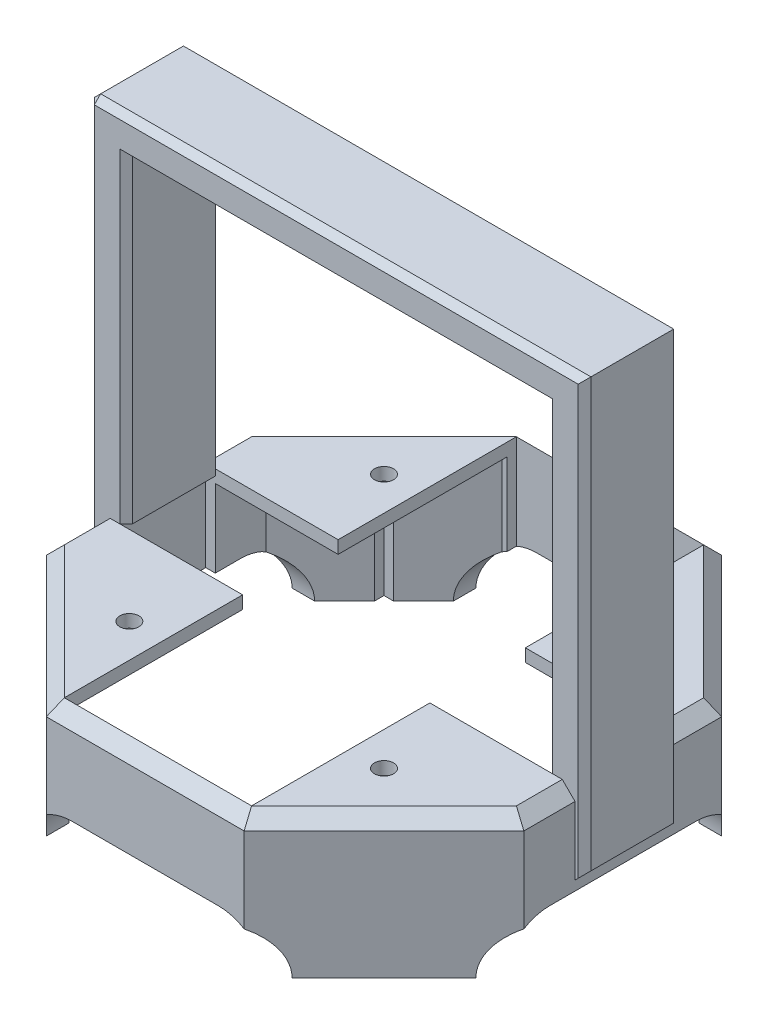
SolidWorks part; units mm, degrees
ref_plane "Front Plane" through (0, 0, 0) normal (0, 0, 1) x (1, 0, 0)
ref_plane "Top Plane" through (0, 0, 0) normal (0, 1, 0) x (1, 0, 0)
ref_plane "Right Plane" through (0, 0, 0) normal (1, 0, 0) x (0, 0, -1)
sketch "Sketch1" plane through (0, 0, 0) normal (0, 1, 0) x (1, 0, 0)
  line L1 (15.533, 37.5) -> (-15.533, 37.5)
  line L2 (-15.533, 37.5) -> (-37.5, 15.533)
  line L3 (-37.5, 15.533) -> (-37.5, -15.533)
  line L4 (-37.5, -15.533) -> (-15.533, -37.5)
  line L5 (-15.533, -37.5) -> (15.533, -37.5)
  line L6 (15.533, -37.5) -> (37.5, -15.533)
  line L7 (37.5, -15.533) -> (37.5, 15.533)
  line L8 (37.5, 15.533) -> (15.533, 37.5)
  circle A0 centre (0, 0) radius 37.5 construction
  dimension "D1" = 75
extrude "Boss-Extrude1" add sketch "Sketch1" along normal blind 50
sketch "Sketch7" plane through (0, 0, 0) normal (0, -1, 0) x (1, 0, 0)
  line L0 (-15.533, 37.5) -> (15.533, 37.5) construction
  line L1 (39, 16.1543) -> (16.1543, 39)
  line L2 (16.1543, 39) -> (-16.1543, 39)
  line L3 (-16.1543, 39) -> (-39, 16.1543)
  line L4 (-39, 16.1543) -> (-39, -16.1543)
  line L5 (-39, -16.1543) -> (-16.1543, -39)
  line L6 (-16.1543, -39) -> (16.1543, -39)
  line L7 (16.1543, -39) -> (39, -16.1543)
  line L8 (39, -16.1543) -> (39, 16.1543)
  circle A0 centre (0, 0) radius 39 construction
  dimension "76" = 78
extrude "Boss-Extrude4" add sketch "Sketch7" along normal blind 55
sketch "Sketch18" plane through (0, 50, 0) normal (0, 1, 0) x (1, 0, 0)
  line L0 (-39, -16.1543) -> (-39, 16.1543) construction
  line L2 (-39, 7.5) -> (-39, -7.5)
  line L12 (-39, 7.5) -> (-33, 7.5)
  line L14 (-33, 7.5) -> (-33, -7.5)
  line L15 (-33, -7.5) -> (-39, -7.5)
  line L16 (0, -55) -> (0, 55) construction
  line L17 (33, 7.5) -> (33, -7.5)
  line L18 (39, 7.5) -> (33, 7.5)
  line L19 (39, 7.5) -> (39, -7.5)
  line L20 (33, -7.5) -> (39, -7.5)
  point P1 (-33, 0)
  dimension "D1" = 15
  dimension "D2" = 6
  dimension "D3" = 6
sketch "Sketch3" plane through (0, 0, 37.5) normal (0, 0, 1) x (1, 0, 0)
  line L0 (-11.5, 28) -> (11.5, 28) construction
  line L1 (-11.5, 35.8) -> (11.5, 35.8)
  line L2 (-11.5, 20.2) -> (11.5, 20.2)
  line L4 (-15.533, 50) -> (15.533, 50) construction
  arc A0 (-11.5, 35.8) -> (-11.5, 20.2) centre (-11.5, 28) ccw
  arc A1 (11.5, 20.2) -> (11.5, 35.8) centre (11.5, 28) ccw
  point P2 (0, 28)
  dimension "D1" = 7.8
  dimension "D2" = 23
  dimension "D3" = 22
extrude "Cut-Extrude1" cut sketch "Sketch3" against normal up to surface (75 mm away) up to face at (0, 25, -37.5)
sketch "Sketch4" plane through (-37.5, 0, 0) normal (-1, 0, 0) x (0, 0, 1)
  line L0 (-11.5, 28) -> (11.5, 28) construction
  line L1 (-11.5, 35.8) -> (11.5, 35.8)
  line L2 (-11.5, 20.2) -> (11.5, 20.2)
  line L4 (-15.533, 50) -> (15.533, 50) construction
  arc A0 (-11.5, 35.8) -> (-11.5, 20.2) centre (-11.5, 28) ccw
  arc A1 (11.5, 20.2) -> (11.5, 35.8) centre (11.5, 28) ccw
  point P2 (0, 28)
  dimension "D1" = 7.8
  dimension "D2" = 22
  dimension "D3" = 23
extrude "Cut-Extrude2" cut sketch "Sketch4" against normal up to surface and the other way up to surface up to face at (39, -27.5, 0) other way up to face at (-39, -27.5, 0)
chamfer "Chamfer5" distance 3 angle 45 8 edges at (-39, 0, 0) (-27.5772, 0, -27.5772) (0, 0, -39) (27.5772, 0, -27.5772) (39, 0, 0) (27.5772, 0, 27.5772) (0, 0, 39) (-27.5772, 0, 27.5772)
shell "Shell1" [suppressed] thickness 2
sketch "Sketch11" plane through (0, 0, -39) normal (0, 0, 1) x (1, 0, 0)
  line L1 (16.1543, -55) -> (-16.1543, -55) construction
  circle A0 centre (0, -17) radius 10
  dimension "D2" = 20
  dimension "D1" = 38
extrude "Cut-Extrude5" cut sketch "Sketch11" along normal up to surface (78 mm away) up to face at (0, -29, 39)
chamfer "Chamfer7" distance 2 angle 45 8 edges at (26.5165, 50, 26.5165) (0, 50, 37.5) (-26.5165, 50, 26.5165) (37.5, 50, 0) (26.5165, 50, -26.5165) (-37.5, 50, 0) (-26.5165, 50, -26.5165) (0, 50, -37.5)
extrude "Boss-Extrude10" add sketch "Sketch18" along normal blind 50 and the other way up to vertex (14.2 mm away) separate body other way up to point (-37.5, 35.8, 11.5)
sketch "Sketch20" plane through (0, 100, 0) normal (0, 1, 0) x (1, 0, 0)
  line L1 (-39, 7.5) -> (39, 7.5)
  line L2 (-39, 7.5) -> (-39, -7.5)
  line L3 (-39, -7.5) -> (39, -7.5)
  line L4 (39, 7.5) -> (39, -7.5)
extrude "Boss-Extrude11" add sketch "Sketch20" along normal blind 6
chamfer "Chamfer8" distance 3 angle 45 2 edges at (-39, 35.8, 0) (39, 35.8, 0)
chamfer "Chamfer9" distance 1 angle 45 13 edges at (-33, 67.9, -7.5) (0, 100, -7.5) (33, 67.9, -7.5) (-33, 67.9, 7.5) (0, 100, 7.5) (33, 67.9, 7.5) (39, 72.4, -7.5) (0, 106, -7.5) (-39, 72.4, -7.5) (-39, 106, 0) (39, 72.4, 7.5) (0, 106, 7.5) (-39, 72.4, 7.5)
sketch "Sketch21" plane through (0, 0, 39) normal (0, 0, 1) x (1, 0, 0)
  line L0 (39, -55) -> (16.1543, -55) construction
  line L1 (-17.5, -35) -> (17.5, -35)
  line L2 (-17.5, -35) -> (-17.5, -55)
  line L3 (-17.5, -55) -> (17.5, -55)
  line L4 (17.5, -35) -> (17.5, -55)
  point P6 (0, -35)
  dimension "D1" = 35
  dimension "D2" = 20
extrude "Cut-Extrude6" cut sketch "Sketch21" against normal up to surface (78 mm away) up to face at (10, -17, -39)
sketch "Sketch22" plane through (-39, 0, 0) normal (-1, 0, 0) x (0, 0, 1)
  line L0 (-16.1543, -55) -> (-16.1543, -3) construction
  line L1 (-16.1543, -41) -> (16.1543, -41)
  line L2 (-16.1543, -41) -> (-16.1543, -55)
  line L3 (-16.1543, -55) -> (16.1543, -55)
  line L4 (16.1543, -41) -> (16.1543, -55)
  dimension "D1" = 14
extrude "Cut-Extrude7" cut sketch "Sketch22" against normal up to surface (78 mm away) up to face at (39, -29, 0)
sketch "Sketch23" plane through (0, 106, 0) normal (0, 1, 0) x (1, 0, 0)
  line L0 (39, 16.1543) -> (39, -16.1543) construction
  line L1 (-39, -39) -> (39, -39)
  line L2 (-39, -39) -> (-39, 39)
  line L3 (-39, 39) -> (39, 39)
  line L4 (39, -39) -> (39, 39)
  line L5 (-39, -39) -> (39, 39) construction
  line L6 (-39, 39) -> (39, -39) construction
  line L7 (-16.1543, 39) -> (16.1543, 39) construction
  point P0 (0, 0)
extrude "Cut-Extrude8" [suppressed] cut sketch "Sketch23" against normal up to vertex
sketch "Sketch25" plane through (0, -55, 0) normal (0, -1, 0) x (1, 0, 0)
  line L0 (-39, -16.1543) -> (-49.5, -16.1543)
  line L1 (-42.5, -22.5) -> (42.5, -22.5) construction
  line L2 (-42.5, -22.5) -> (-42.5, 22.5) construction
  line L3 (-42.5, 22.5) -> (42.5, 22.5) construction
  line L4 (42.5, -22.5) -> (42.5, 22.5) construction
  line L5 (-42.5, -22.5) -> (42.5, 22.5) construction
  line L6 (-42.5, 22.5) -> (42.5, -22.5) construction
  line L7 (-49.5, -16.1543) -> (-49.5, -29.5)
  line L8 (-49.5, -29.5) -> (-25.6543, -29.5)
  line L9 (-39, -16.1543) -> (-17.5, -37.6543) construction
  line L12 (-39, -16.1543) -> (-25.6543, -29.5)
  line L13 (55, 0) -> (-55, 0) construction
  line L14 (-39, 16.1543) -> (-49.5, 16.1543)
  line L15 (-49.5, 16.1543) -> (-49.5, 29.5)
  line L16 (-49.5, 29.5) -> (-25.6543, 29.5)
  line L17 (-39, 16.1543) -> (-25.6543, 29.5)
  line L18 (0, -55) -> (0, 55) construction
  line L19 (39, -16.1543) -> (49.5, -16.1543)
  line L20 (49.5, -16.1543) -> (49.5, -29.5)
  line L21 (49.5, -29.5) -> (25.6543, -29.5)
  line L22 (39, -16.1543) -> (25.6543, -29.5)
  line L23 (39, 16.1543) -> (25.6543, 29.5)
  line L24 (49.5, 29.5) -> (25.6543, 29.5)
  line L25 (49.5, 16.1543) -> (49.5, 29.5)
  line L26 (39, 16.1543) -> (49.5, 16.1543)
  circle A0 centre (-42.5, 22.5) radius 1.5
  circle A1 centre (42.5, 22.5) radius 1.5
  circle A2 centre (42.5, -22.5) radius 1.5
  circle A3 centre (-42.5, -22.5) radius 1.5
  point P0 (0, 0)
  dimension "D3" = 3
  dimension "D1" = 85
  dimension "D2" = 45
  dimension "D4" = 7
  dimension "D5" = 7
extrude "Boss-Extrude12" add sketch "Sketch25" against normal blind 5
sketch "Sketch26" plane through (0, 50, 0) normal (0, 1, 0) x (1, 0, 0)
  line L1 (-14.7046, 35.5) -> (14.7046, 35.5)
  line L2 (-14.7046, 35.5) -> (-14.7046, -35.5)
  line L3 (-14.7046, -35.5) -> (14.7046, -35.5)
  line L4 (14.7046, 35.5) -> (14.7046, -35.5)
extrude "Cut-Extrude9" cut sketch "Sketch26" against normal blind 15
sketch "Sketch27" plane through (0, 50, 0) normal (0, 1, 0) x (1, 0, 0)
  line L1 (35.5, 7.5) -> (-35.5, 7.5)
  line L2 (35.5, 7.5) -> (35.5, -7.5)
  line L3 (35.5, -7.5) -> (-35.5, -7.5)
  line L4 (-35.5, 7.5) -> (-35.5, -7.5)
  line L5 (-35.5, 14.7046) -> (-35.5, -14.7046) construction
  line L6 (35.5, -14.7046) -> (35.5, 14.7046) construction
  line L7 (14.7046, -35.5) -> (14.7046, 35.5) construction
  point P10 (14.7046, 0)
  point P11 (35.5, 0)
  dimension "D1" = 15
extrude "Cut-Extrude10" cut sketch "Sketch27" against normal blind 15
chamfer "Chamfer10" distance 8 angle 45 4 edges at (49.5, -52.5, 29.5) (49.5, -52.5, -29.5) (-49.5, -52.5, -29.5) (-49.5, -52.5, 29.5)
sketch "Sketch28" plane through (0, -55, 0) normal (0, -1, 0) x (1, 0, 0)
  line L0 (41.5, 29.5) -> (25.6543, 29.5) construction
  line L1 (39, 29.5) -> (49.5, 29.5)
  line L2 (39, 29.5) -> (39, -29.5)
  line L3 (39, -29.5) -> (49.5, -29.5)
  line L4 (49.5, 29.5) -> (49.5, -29.5)
  line L5 (25.6543, -29.5) -> (41.5, -29.5) construction
  line L6 (39, -16.1543) -> (39, 16.1543) construction
  line L7 (49.5, 16.1543) -> (49.5, 21.5) construction
  line L8 (0, -55) -> (0, 55) construction
  line L9 (-39, -29.5) -> (-49.5, -29.5)
  line L10 (-49.5, 29.5) -> (-49.5, -29.5)
  line L11 (-39, 29.5) -> (-49.5, 29.5)
  line L12 (-39, 29.5) -> (-39, -29.5)
extrude "Cut-Extrude11" cut sketch "Sketch28" against normal blind 2
sketch "Sketch29" plane through (0, -50, 0) normal (0, 1, 0) x (1, 0, 0)
  circle A0 centre (-42.5, 22.5) radius 3
  circle A1 centre (42.5, 22.5) radius 3
  circle A2 centre (42.5, -22.5) radius 3
  circle A3 centre (-42.5, -22.5) radius 3
  dimension "D1" = 6
extrude "Cut-Extrude12" cut sketch "Sketch29" against normal blind 1
sketch "Sketch30" plane through (0, -55, 0) normal (0, -1, 0) x (1, 0, 0)
  line L0 (-16.1543, -39) -> (16.1543, -39) construction
  line L1 (-49.5, 39) -> (49.5, 39)
  line L2 (-49.5, 39) -> (-49.5, -39)
  line L3 (-49.5, -39) -> (49.5, -39)
  line L4 (49.5, 39) -> (49.5, -39)
  line L5 (16.1543, 39) -> (-16.1543, 39) construction
  line L6 (-49.5, -16.1543) -> (-49.5, -21.5) construction
  line L7 (49.5, -21.5) -> (49.5, -16.1543) construction
extrude "Cut-Extrude13" cut sketch "Sketch30" against normal blind 83
sketch "Sketch31" plane through (0, 50, 0) normal (0, 1, 0) x (1, 0, 0)
  line L1 (-20, -20) -> (20, -20) construction
  line L2 (-20, -20) -> (-20, 20) construction
  line L3 (-20, 20) -> (20, 20) construction
  line L4 (20, -20) -> (20, 20) construction
  circle A0 centre (-20, 20) radius 1.5
  circle A1 centre (20, 20) radius 1.5
  circle A2 centre (20, -20) radius 1.5
  circle A3 centre (-20, -20) radius 1.5
  point P0 (0, 20)
  point P7 (20, 0)
  dimension "D2" = 3
  dimension "D1" = 40
extrude "Cut-Extrude14" cut sketch "Sketch31" against normal up to surface (22 mm away) up to face at (-24.111, 28, -24.111)
sketch "Sketch32" plane through (0, 28, 0) normal (0, -1, 0) x (1, 0, 0)
  line L9 (-25.5, -25.5) -> (25.5, -25.5)
  line L10 (-25.5, -25.5) -> (-25.5, 25.5)
  line L11 (-25.5, 25.5) -> (25.5, 25.5)
  line L12 (25.5, -25.5) -> (25.5, 25.5)
  point P0 (0, 25.5)
  point P7 (25.5, 0)
  dimension "D1" = 51
extrude "Cut-Extrude15" cut sketch "Sketch32" against normal blind 20 contours L10 L9 L12 L11
sketch "Sketch34" plane through (0, 28, 0) normal (0, -1, 0) x (1, 0, 0)
  line L0 (-34, 15.4975) -> (-15.4975, 34)
  line L1 (-15.4975, 34) -> (15.4975, 34)
  line L2 (15.4975, 34) -> (34, 15.4975)
  line L3 (34, 15.4975) -> (34, -15.4975)
  line L4 (34, -15.4975) -> (15.4975, -34)
  line L5 (15.4975, -34) -> (-15.4975, -34)
  line L6 (-15.4975, -34) -> (-34, -15.4975)
  line L7 (-34, -15.4975) -> (-34, 15.4975)
  line L9 (-19.3, 33.733) -> (-33.733, 19.3) construction
  line L11 (33.733, 19.3) -> (19.3, 33.733) construction
  line L13 (0, 34) -> (0, -34) construction
  line L15 (-33.733, 19.3) -> (-37.5, 15.533) construction
  point P3 (0, 34)
  point P10 (34, 0)
  dimension "D1" = 68
  dimension "D2" = 68
  dimension "D3" = 2.5
extrude "Cut-Extrude16" cut sketch "Sketch34" against normal blind 20
